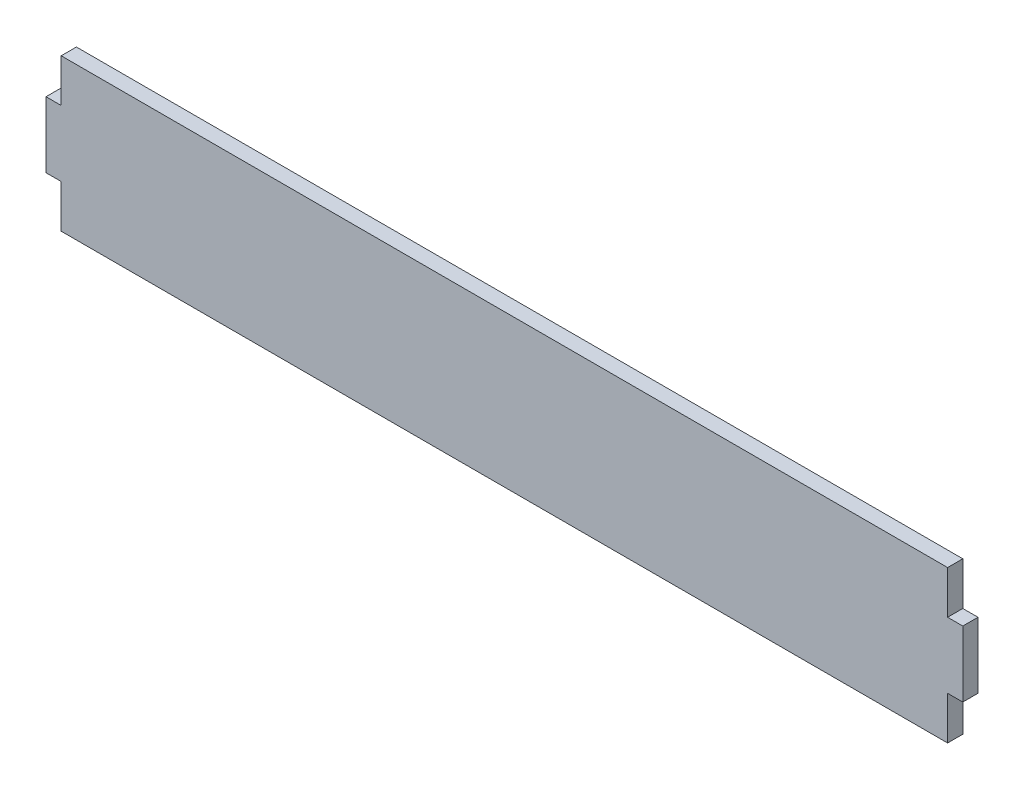
SolidWorks part; units mm, degrees
ref_plane "Front Plane" through (0, 0, 0) normal (0, 0, 1) x (1, 0, 0)
ref_plane "Top Plane" through (0, 0, 0) normal (0, 1, 0) x (1, 0, 0)
ref_plane "Right Plane" through (0, 0, 0) normal (1, 0, 0) x (0, 0, -1)
sketch "Sketch1" plane through (0, 0, 0) normal (0, 0, 1) x (1, 0, 0)
  line L0 (3, 21.5) -> (3, 30)
  line L1 (3, 0) -> (178, 0)
  line L3 (3, 30) -> (178, 30)
  line L5 (0, 21.5) -> (3, 21.5)
  line L6 (0, 21.5) -> (0, 8.5)
  line L7 (0, 8.5) -> (3, 8.5)
  line L10 (0, 0) -> (3, 0) construction
  line L11 (3, 8.5) -> (3, 0)
  line L12 (0, 8.5) -> (0, 0) construction
  line L13 (90.5, 15) -> (90.5, 3.5137) construction
  line L14 (0, 15) -> (181, 15) construction
  line L15 (181, -81.0403) -> (181, 52.114) construction
  line L16 (178, 8.5) -> (178, 0)
  line L17 (181, 8.5) -> (178, 8.5)
  line L18 (178, 21.5) -> (178, 30)
  line L19 (181, 21.5) -> (178, 21.5)
  line L20 (181, 21.5) -> (181, 8.5)
  point P1 (178, 30)
  point P4 (200.7901, 15)
  point P16 (188.679, 15)
  dimension "D1" = 30
  dimension "D2" = 13
  dimension "D3" = 3
extrude "Boss-Extrude1" add sketch "Sketch1" along normal blind 3
